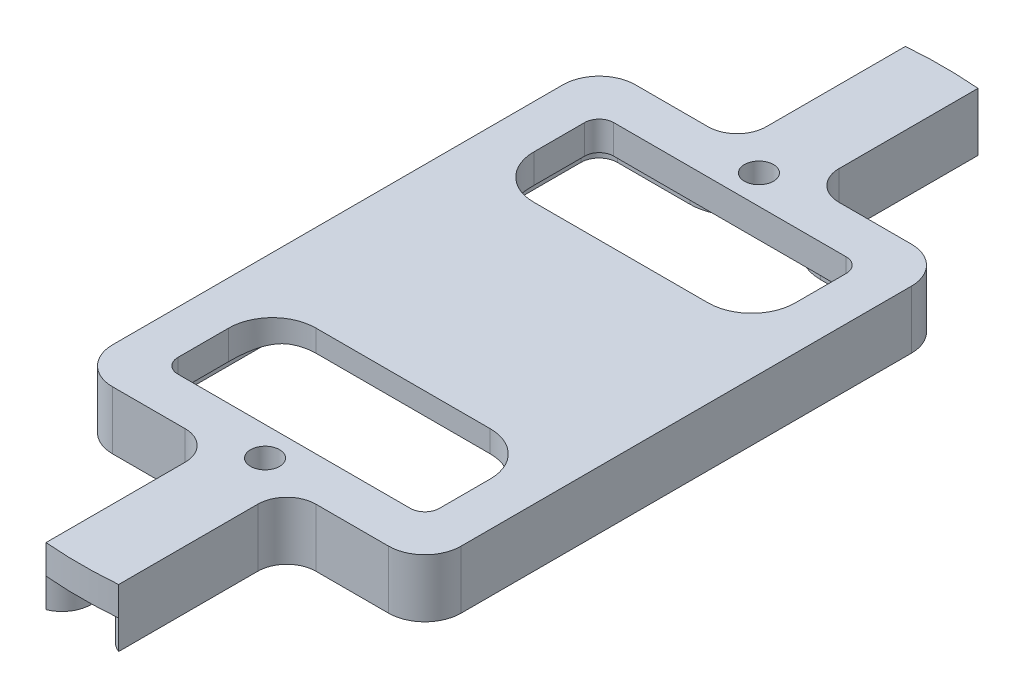
SolidWorks part; units mm, degrees
ref_plane "Front Plane" through (0, 0, 0) normal (0, 0, 1) x (1, 0, 0)
ref_plane "Top Plane" through (0, 0, 0) normal (0, 1, 0) x (1, 0, 0)
ref_plane "Right Plane" through (0, 0, 0) normal (1, 0, 0) x (0, 0, -1)
sketch "Sketch2" plane through (0, 92, 0) normal (0, 1, 0) x (1, 0, 0)
  line L10 (8, 15) -> (-8, 15) construction
  line L11 (9, -14) -> (9, 14) construction
  line L12 (-8, -15) -> (8, -15) construction
  line L13 (-9, 14) -> (-9, -14) construction
  line L14 (8, 15) -> (-8, 15)
  line L15 (9, -14) -> (9, 14)
  line L16 (-8, -15) -> (8, -15)
  line L17 (-9, 14) -> (-9, -14)
  line L50 (-9.5, -18) -> (-4.5, -18)
  line L51 (-2.5, -20) -> (-2.5, -29.5795)
  line L52 (2.5, -29.5795) -> (2.5, -20)
  line L53 (4.5, -18) -> (9.5, -18)
  line L54 (12, -15.5) -> (12, 15.5)
  line L55 (9.5, 18) -> (4.5, 18)
  line L56 (2.5, 20) -> (2.5, 29.5795)
  line L57 (-2.5, 29.5795) -> (-2.5, 20)
  line L58 (-4.5, 18) -> (-9.5, 18)
  line L60 (-12, 15.5) -> (-12, -15.5)
  circle A0 centre (0, 0) radius 29.685 construction
  arc A1 (-2.5, -29.5795) -> (2.5, -29.5795) centre (0, 0) ccw
  arc A2 (-8, 15) -> (-9, 14) centre (-8, 14) ccw construction
  arc A3 (9, 14) -> (8, 15) centre (8, 14) ccw construction
  arc A4 (2.5, 29.5795) -> (-2.5, 29.5795) centre (0, 0) ccw
  arc A8 (8, -15) -> (9, -14) centre (8, -14) ccw construction
  arc A9 (-9, -14) -> (-8, -15) centre (-8, -14) ccw construction
  arc A10 (-8, 15) -> (-9, 14) centre (-8, 14) ccw
  arc A11 (9, 14) -> (8, 15) centre (8, 14) ccw
  arc A12 (8, -15) -> (9, -14) centre (8, -14) ccw
  arc A13 (-9, -14) -> (-8, -15) centre (-8, -14) ccw
  arc A34 (2.5, 20) -> (4.5, 18) centre (4.5, 20) ccw
  arc A50 (-4.5, 18) -> (-2.5, 20) centre (-4.5, 20) ccw
  arc A62 (9.5, -18) -> (12, -15.5) centre (9.5, -15.5) ccw
  arc A63 (12, 15.5) -> (9.5, 18) centre (9.5, 15.5) ccw
  arc A67 (-9.5, 18) -> (-12, 15.5) centre (-9.5, 15.5) ccw
  arc A68 (-12, -15.5) -> (-9.5, -18) centre (-9.5, -15.5) ccw
  arc A83 (-2.5, -20) -> (-4.5, -18) centre (-4.5, -20) ccw
  arc A85 (4.5, -18) -> (2.5, -20) centre (4.5, -20) ccw
extrude "Battery holder outline" add sketch "Sketch2" along normal blind 2
sketch "Sketch3" plane through (0, 92, 0) normal (0, -1, 0) x (1, 0, 0)
  line L24 (2.5, 20) -> (2.5, 29.5795)
  line L25 (9.5, 18) -> (4.5, 18)
  line L26 (12, -15.5) -> (12, 15.5)
  line L27 (4.5, -18) -> (9.5, -18)
  line L28 (2.5, -29.5795) -> (2.5, -20)
  line L29 (-2.5, -20) -> (-2.5, -29.5795)
  line L40 (-9.5, -18) -> (-4.5, -18)
  line L41 (-12, 15.5) -> (-12, -15.5)
  line L42 (-4.5, 18) -> (-9.5, 18)
  line L43 (-2.5, 29.5795) -> (-2.5, 20)
  line L44 (2.5, 20) -> (2.5, 29.5795)
  line L45 (9.5, 18) -> (4.5, 18)
  line L46 (12, -15.5) -> (12, 15.5)
  line L47 (4.5, -18) -> (9.5, -18)
  line L48 (2.5, -29.5795) -> (2.5, -20)
  line L49 (-2.5, -20) -> (-2.5, -29.5795)
  line L60 (-9.5, -18) -> (-4.5, -18)
  line L61 (-12, 15.5) -> (-12, -15.5)
  line L62 (-4.5, 18) -> (-9.5, 18)
  line L63 (-2.5, 29.5795) -> (-2.5, 20)
  line L64 (1.25, -28.4075) -> (1.25, -29.6587)
  line L65 (-1.25, -28.4075) -> (-1.25, -29.6587)
  line L66 (1.25, 28.4075) -> (1.25, 29.6587)
  line L67 (-1.25, 28.4075) -> (-1.25, 29.6587)
  line L74 (1.25, 20) -> (1.25, 28.4075)
  line L75 (9.5, 16.75) -> (4.5, 16.75)
  line L76 (10.75, -15.5) -> (10.75, 15.5)
  line L77 (4.5, -16.75) -> (9.5, -16.75)
  line L78 (1.25, -28.4075) -> (1.25, -20)
  line L79 (-1.25, -20) -> (-1.25, -28.4075)
  line L80 (-9.5, -16.75) -> (-4.5, -16.75)
  line L81 (-10.75, 15.5) -> (-10.75, -15.5)
  line L82 (-4.5, 16.75) -> (-9.5, 16.75)
  line L83 (-1.25, 28.4075) -> (-1.25, 20)
  line L84 (1.25, 20) -> (1.25, 28.4075)
  line L85 (9.5, 16.75) -> (4.5, 16.75)
  line L86 (10.75, -15.5) -> (10.75, 15.5)
  line L87 (4.5, -16.75) -> (9.5, -16.75)
  line L88 (1.25, -28.4075) -> (1.25, -20)
  line L89 (-1.25, -20) -> (-1.25, -28.4075)
  line L90 (-9.5, -16.75) -> (-4.5, -16.75)
  line L91 (-10.75, 15.5) -> (-10.75, -15.5)
  line L92 (-4.5, 16.75) -> (-9.5, 16.75)
  line L93 (-1.25, 28.4075) -> (-1.25, 20)
  arc A12 (-2.5, -29.5795) -> (2.5, -29.5795) centre (0, 0) ccw
  arc A13 (-2.5, -29.5795) -> (-1.25, -29.6587) centre (0, 0) ccw
  arc A14 (2.5, 29.5795) -> (-2.5, 29.5795) centre (0, 0) ccw
  arc A15 (2.5, 29.5795) -> (1.25, 29.6587) centre (0, 0) ccw
  arc A16 (-1.25, -28.4075) -> (1.25, -28.4075) centre (0, 0) ccw
  arc A18 (1.25, 28.4075) -> (-1.25, 28.4075) centre (0, 0) ccw
  arc A23 (2.5, 20) -> (4.5, 18) centre (4.5, 20) ccw
  arc A24 (12, 15.5) -> (9.5, 18) centre (9.5, 15.5) ccw
  arc A25 (9.5, -18) -> (12, -15.5) centre (9.5, -15.5) ccw
  arc A26 (4.5, -18) -> (2.5, -20) centre (4.5, -20) ccw
  arc A28 (-2.5, -20) -> (-4.5, -18) centre (-4.5, -20) ccw
  arc A29 (-12, -15.5) -> (-9.5, -18) centre (-9.5, -15.5) ccw
  arc A40 (-9.5, 18) -> (-12, 15.5) centre (-9.5, 15.5) ccw
  arc A41 (-4.5, 18) -> (-2.5, 20) centre (-4.5, 20) ccw
  arc A43 (2.5, 20) -> (4.5, 18) centre (4.5, 20) ccw
  arc A44 (12, 15.5) -> (9.5, 18) centre (9.5, 15.5) ccw
  arc A45 (9.5, -18) -> (12, -15.5) centre (9.5, -15.5) ccw
  arc A46 (4.5, -18) -> (2.5, -20) centre (4.5, -20) ccw
  arc A48 (-2.5, -20) -> (-4.5, -18) centre (-4.5, -20) ccw
  arc A49 (-12, -15.5) -> (-9.5, -18) centre (-9.5, -15.5) ccw
  arc A60 (-9.5, 18) -> (-12, 15.5) centre (-9.5, 15.5) ccw
  arc A61 (-4.5, 18) -> (-2.5, 20) centre (-4.5, 20) ccw
  arc A62 (-1.25, 29.6587) -> (-2.5, 29.5795) centre (0, 0) ccw
  arc A63 (1.25, -29.6587) -> (2.5, -29.5795) centre (0, 0) ccw
  arc A73 (1.25, 20) -> (4.5, 16.75) centre (4.5, 20) ccw
  arc A74 (10.75, 15.5) -> (9.5, 16.75) centre (9.5, 15.5) ccw
  arc A75 (9.5, -16.75) -> (10.75, -15.5) centre (9.5, -15.5) ccw
  arc A76 (4.5, -16.75) -> (1.25, -20) centre (4.5, -20) ccw
  arc A78 (-1.25, -20) -> (-4.5, -16.75) centre (-4.5, -20) ccw
  arc A79 (-10.75, -15.5) -> (-9.5, -16.75) centre (-9.5, -15.5) ccw
  arc A80 (-9.5, 16.75) -> (-10.75, 15.5) centre (-9.5, 15.5) ccw
  arc A81 (-4.5, 16.75) -> (-1.25, 20) centre (-4.5, 20) ccw
  arc A83 (1.25, 20) -> (4.5, 16.75) centre (4.5, 20) ccw
  arc A84 (10.75, 15.5) -> (9.5, 16.75) centre (9.5, 15.5) ccw
  arc A85 (9.5, -16.75) -> (10.75, -15.5) centre (9.5, -15.5) ccw
  arc A86 (4.5, -16.75) -> (1.25, -20) centre (4.5, -20) ccw
  arc A88 (-1.25, -20) -> (-4.5, -16.75) centre (-4.5, -20) ccw
  arc A89 (-10.75, -15.5) -> (-9.5, -16.75) centre (-9.5, -15.5) ccw
  arc A90 (-9.5, 16.75) -> (-10.75, 15.5) centre (-9.5, 15.5) ccw
  arc A91 (-4.5, 16.75) -> (-1.25, 20) centre (-4.5, 20) ccw
  dimension "D1" = 0
  dimension "D2" = 1.25
extrude "Lip" add sketch "Sketch3" along normal blind 2
sketch "Sketch4" plane through (0, 94, 0) normal (0, 1, 0) x (1, 0, 0)
  line L3 (-8, -15) -> (8, -15) construction
  line L4 (8, 15) -> (-8, 15) construction
  circle A0 centre (0, 17) radius 1
  circle A1 centre (0, -17) radius 1
  dimension "D1" = 2
  dimension "D2" = 2
  dimension "D3" = 2
extrude "Screwhole" cut sketch "Sketch4" against normal blind 10
sketch "Sketch5" plane through (0, 94, 0) normal (0, 1, 0) x (1, 0, 0)
  line L0 (-9, 14) -> (-9, -14) construction
  line L1 (-9, 7.5) -> (9, 7.5)
  line L2 (-9, 7.5) -> (-9, -7.5)
  line L3 (-9, -7.5) -> (9, -7.5)
  line L4 (9, 7.5) -> (9, -7.5)
  line L5 (9, -14) -> (9, 14) construction
  point P8 (9, 0)
  dimension "D1" = 15
extrude "Actual battery cap thingy" add sketch "Sketch5" against normal blind 1.5
fillet "Fillets for the thing above" radius 3 6 edges at (9, 93.25, 7.5) (-9, 93.25, 7.5) (-9, 93.25, -7.5) (9, 93.25, -7.5) (-9, 92.5, 0) (9, 92.5, 0)
fillet "Fillets at edge" radius 2 4 edges at (-1.25, 91, -29.6587) (1.25, 91, -29.6587) (1.25, 91, 29.6587) (-1.25, 91, 29.6587)
